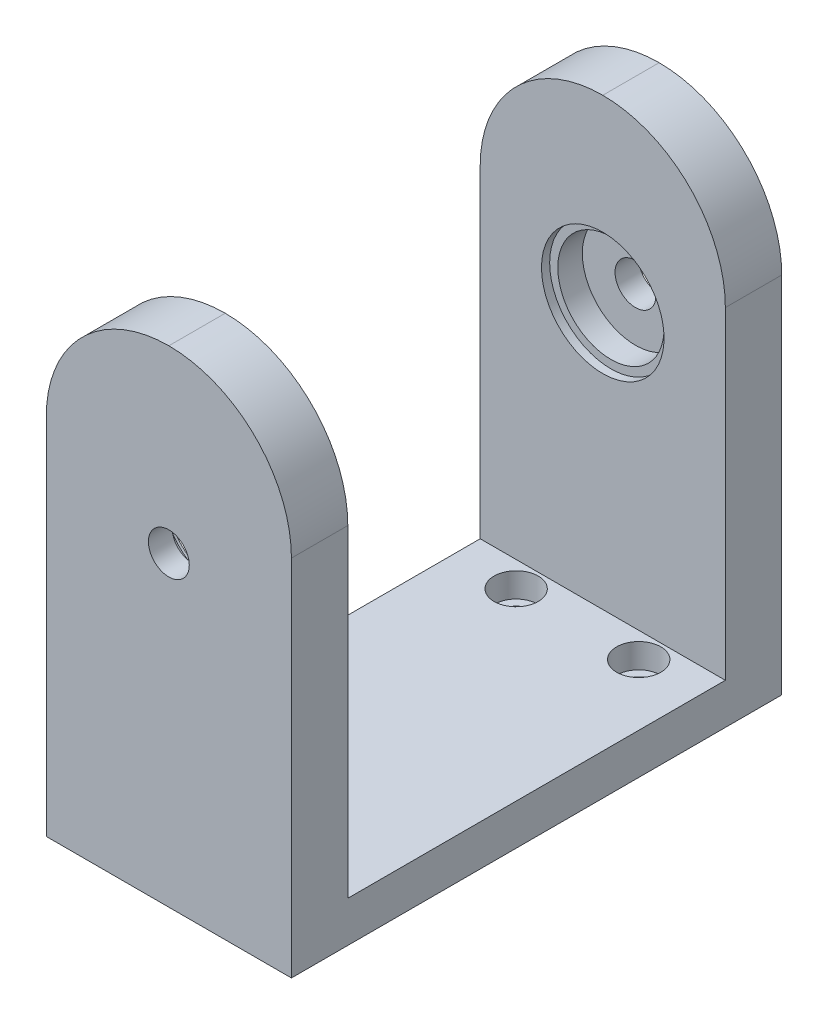
SolidWorks part; units mm, degrees
ref_plane "Front Plane" through (0, 0, 0) normal (0, 0, 1) x (1, 0, 0)
ref_plane "Top Plane" through (0, 0, 0) normal (0, 1, 0) x (1, 0, 0)
ref_plane "Right Plane" through (0, 0, 0) normal (1, 0, 0) x (0, 0, -1)
sketch "Sketch1" plane through (0, 0, 0) normal (0, 1, 0) x (1, 0, 0)
  line L0 (-1.3042, 0) -> (2.0884, 0) construction
  line L1 (0, 5.5134) -> (0, -5.3226) construction
  line L2 (15, 20) -> (-15, 20) construction
  line L3 (15, -30) -> (-15, -30)
  line L4 (15, -30) -> (15, 30)
  line L5 (15, 30) -> (-15, 30)
  line L6 (-15, -30) -> (-15, 30)
  line L7 (15, -30) -> (-15, 30) construction
  line L8 (15, 30) -> (-15, -30) construction
  line L9 (15, -20) -> (-15, -20) construction
  circle A0 centre (-7.5, 20) radius 1.65
  circle A1 centre (7.5, 20) radius 1.65
  circle A2 centre (7.5, -20) radius 1.65
  circle A3 centre (-7.5, -20) radius 1.65
  point P4 (0, 0)
  dimension "D4" = 3.3
  dimension "D1" = 10
  dimension "D2" = 40
  dimension "D3" = 30
  dimension "D5" = 15
extrude "Boss-Extrude1" add sketch "Sketch1" along normal blind 5
sketch "Sketch7" plane through (0, 5, 0) normal (0, 1, 0) x (1, 0, 0)
  circle A0 centre (-7.5, 20) radius 2.7
  circle A1 centre (7.5, 20) radius 2.7
  circle A2 centre (-7.5, -20) radius 2.7
  circle A3 centre (7.5, -20) radius 2.7
  dimension "D1" = 5.4
extrude "Cut-Extrude3" cut sketch "Sketch7" against normal blind 3
ref_plane "Plane1" through (0, 0, 30) normal (0, 0, 1) x (1, 0, 0)
sketch "Sketch3" plane through (0, 0, 30) normal (0, 0, 1) x (1, 0, 0)
  line L0 (-15, 5) -> (15, 5)
  line L1 (15, 5) -> (15, 0) construction
  line L2 (-15, 5) -> (15, 5) construction
  line L3 (15, 5) -> (15, 37.5)
  line L4 (-15, 5) -> (-15, 37.5)
  line L5 (-15, 37.5) -> (-15, 59.5)
  line L6 (15, 37.5) -> (15, 59.5)
  line L7 (15, 59.5) -> (-15, 59.5)
  circle A1 centre (0, 37.5) radius 2.5
  circle A2 centre (0, 37.5) radius 22.5 construction
  dimension "D1" = 5
  dimension "D3" = 45
  dimension "D2" = 37.5
  dimension "D4" = 22
extrude "Boss-Extrude2" add sketch "Sketch3" against normal blind 6.9
sketch "Sketch4" plane through (0, 0, 23.1) normal (0, 0, -1) x (-1, 0, 0)
  circle A0 centre (0, 37.5) radius 7.5
  dimension "D1" = 15
extrude "Cut-Extrude1" cut sketch "Sketch4" against normal blind 1
sketch "Sketch6" plane through (0, 0, 24.1) normal (0, 0, -1) x (-1, 0, 0)
  circle A0 centre (0, 37.5) radius 6.5
  dimension "D1" = 13
extrude "Cut-Extrude2" cut sketch "Sketch6" against normal blind 3
mirror "Mirror2" about plane through (0, 0, 0) normal (0, 0, 1) of "Cut-Extrude2", "Cut-Extrude1", "Boss-Extrude2"
fillet "Fillet1" radius 15 4 edges at (15, 59.5, -26.55) (-15, 59.5, -26.55) (-15, 59.5, 26.55) (15, 59.5, 26.55)
